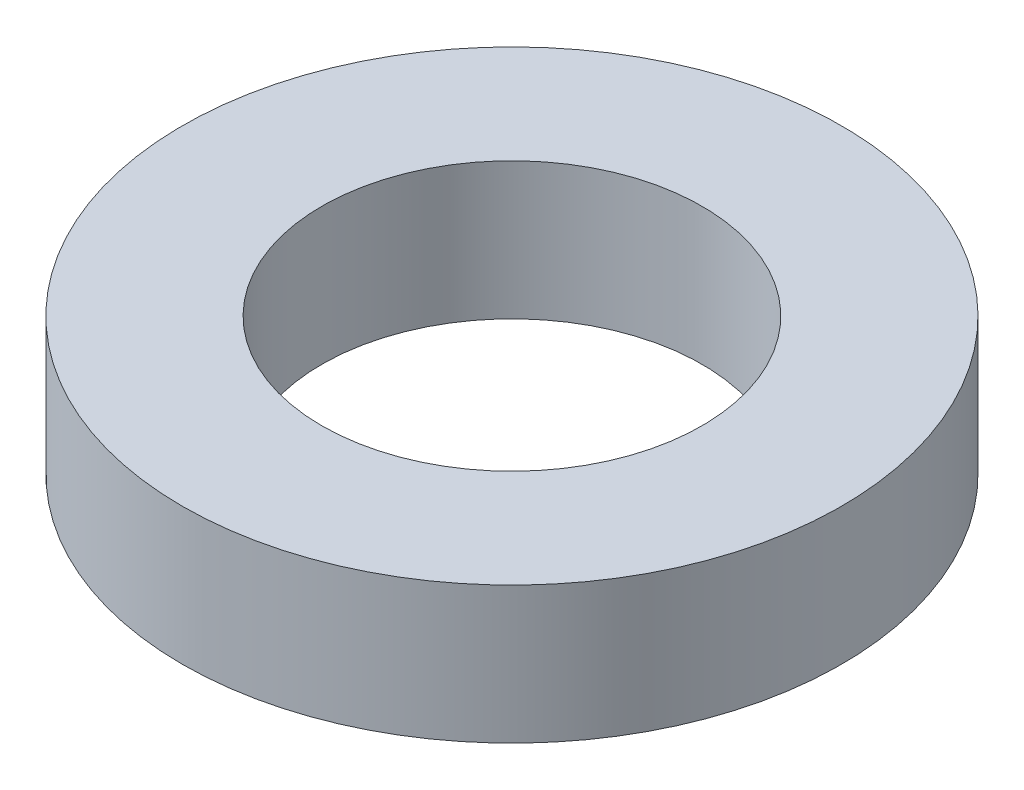
SolidWorks part; units mm, degrees
ref_plane "Front Plane" through (0, 0, 0) normal (0, 0, 1) x (1, 0, 0)
ref_plane "Top Plane" through (0, 0, 0) normal (0, 1, 0) x (1, 0, 0)
ref_plane "Right Plane" through (0, 0, 0) normal (1, 0, 0) x (0, 0, -1)
sketch "Sketch1" plane through (0, 0, 0) normal (0, 1, 0) x (1, 0, 0)
  circle A0 centre (0, 0) radius 65
  dimension "FLANGE_OD" = 130
extrude "Boss-Extrude1" add sketch "Sketch1" along normal blind 27
sketch "Sketch2" plane through (0, 0, 0) normal (0, 1, 0) x (1, 0, 0)
  circle A0 centre (0, 0) radius 37.5
  dimension "BORE_D" = 75
extrude "Cut-Extrude1" cut sketch "Sketch2" along normal through all
sketch "Sketch3" plane through (0, 27, 0) normal (0, 1, 0) x (1, 0, 0)
  circle A0 centre (0, 0) radius 27.446 construction
  circle A1 centre (-27.446, 0) radius 3.5908
  dimension "BOLT_D" = 7.1817
  dimension "BOLT_PCD" = 54.8921
extrude "Cut-Extrude2" cut sketch "Sketch3" against normal blind 23.618 rebuild error yes
pattern_circular "CirPattern1" count 8 over 360 rebuild error yes
